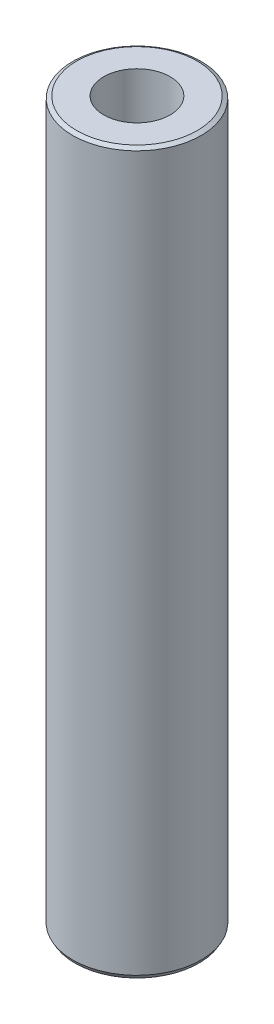
SolidWorks part; units mm, degrees
ref_plane "Front Plane" through (0, 0, 0) normal (0, 0, 1) x (1, 0, 0)
ref_plane "Top Plane" through (0, 0, 0) normal (0, 1, 0) x (1, 0, 0)
ref_plane "Right Plane" through (0, 0, 0) normal (1, 0, 0) x (0, 0, -1)
sketch "Sketch1" plane through (0, 0, 0) normal (0, 1, 0) x (1, 0, 0)
  circle A0 centre (0, 0) radius 35
  dimension "SHAFT_OD" = 70
extrude "Boss-Extrude1" add sketch "Sketch1" along normal blind 392.4961
sketch "Sketch2" plane through (0, 0, 0) normal (0, 1, 0) x (1, 0, 0)
  circle A0 centre (0, 0) radius 18.0885
  dimension "BORE_D" = 36.1769
extrude "Cut-Extrude1" cut sketch "Sketch2" along normal through all
chamfer "Chamfer1" distance 1.2375 angle 60 2 edges at (0, 392.4961, 35) (0, 0, 35) first distance on face at (0, 392.4961, 35) first distance on face at (0, 0, 18.0885)
